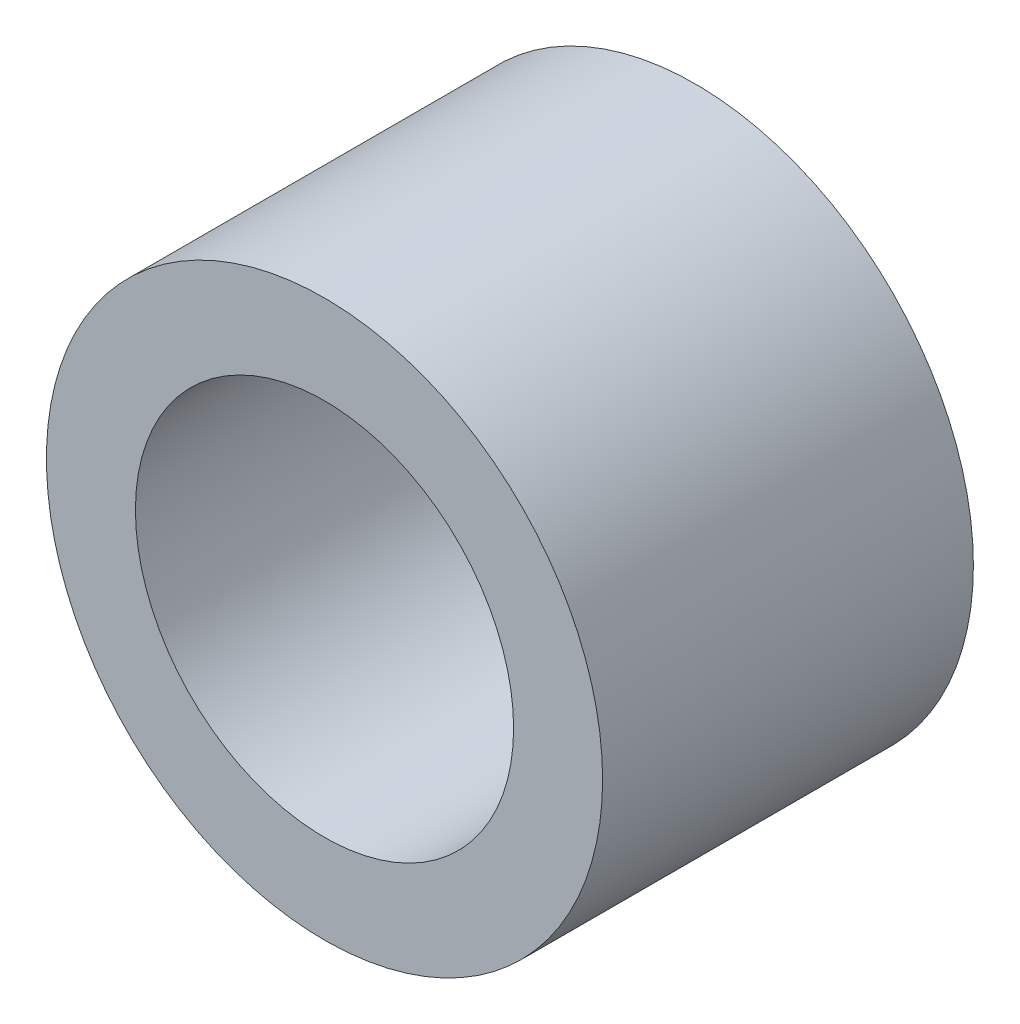
SolidWorks part; units mm, degrees
material "AISI 304"
ref_plane "Front Plane" through (0, 0, 0) normal (0, 0, 1) x (1, 0, 0)
ref_plane "Top Plane" through (0, 0, 0) normal (0, 1, 0) x (1, 0, 0)
ref_plane "Right Plane" through (0, 0, 0) normal (1, 0, 0) x (0, 0, -1)
sketch "Bush_Profile" plane through (0, 0, 0) normal (0, 0, 1) x (1, 0, 0)
  circle A0 centre (0, 0) radius 15
  circle A1 centre (0, 0) radius 10.2
  dimension "Bush_ID" = 20.4
  dimension "Bush_OD" = 30
extrude "Bush_Extrude" add sketch "Bush_Profile" along normal mid plane 20
ref_axis "Bush_Axis" through (0, 0, -11) along (0, 0, 1)
